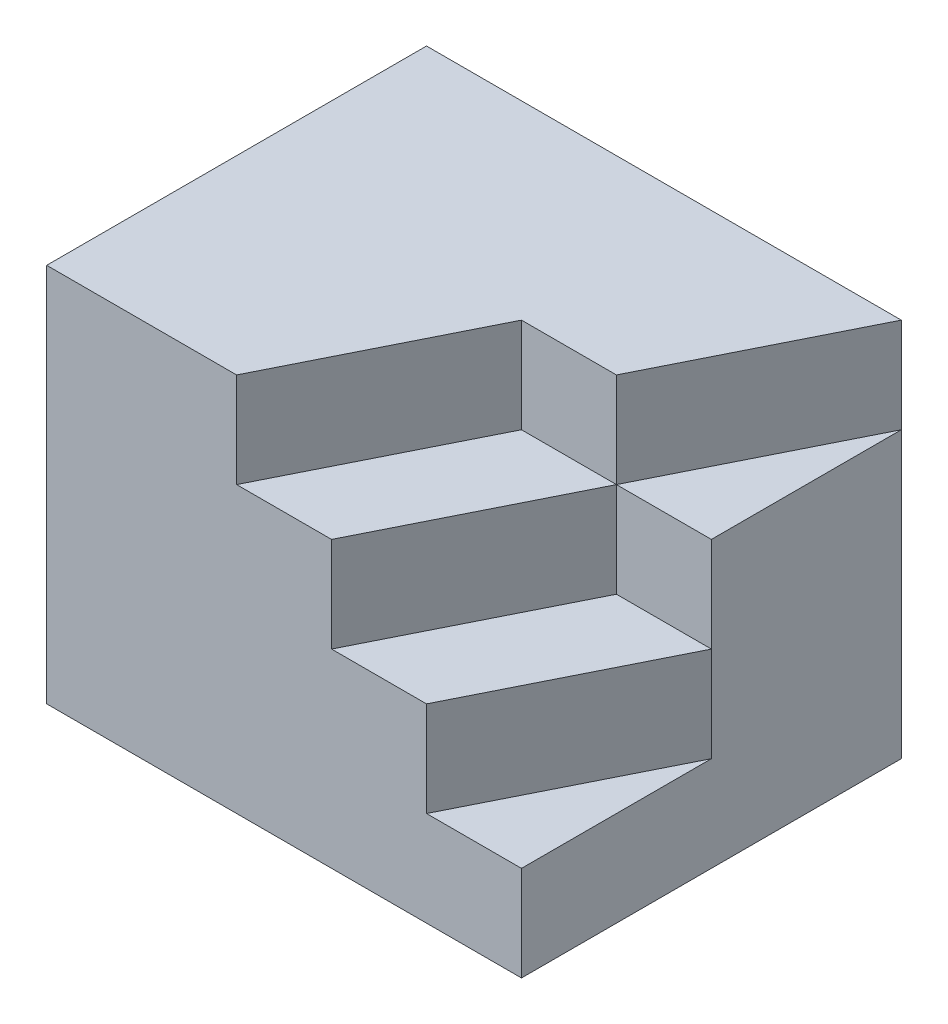
SolidWorks part; units mm, degrees
ref_plane "前基準面" through (0, 0, 0) normal (0, 0, 1) x (1, 0, 0)
ref_plane "上基準面" through (0, 0, 0) normal (0, 1, 0) x (1, 0, 0)
ref_plane "右基準面" through (0, 0, 0) normal (1, 0, 0) x (0, 0, -1)
sketch "草圖1" plane through (0, 0, 0) normal (0, 1, 0) x (1, 0, 0)
  line L1 (-25, -20) -> (25, -20)
  line L2 (-25, -20) -> (-25, 20)
  line L3 (-25, 20) -> (25, 20)
  line L4 (25, -20) -> (25, 20)
  line L5 (-25, -20) -> (25, 20) construction
  line L6 (-25, 20) -> (25, -20) construction
  point P0 (0, 0)
  dimension "D1" = 40
  dimension "D2" = 50
extrude "填料-伸長1" add sketch "草圖1" along normal blind 40
sketch "草圖2" plane through (0, 40, 0) normal (0, 1, 0) x (1, 0, 0)
  line L0 (25, 0) -> (15, -20)
  line L1 (25, -20) -> (25, 20) construction
  line L2 (-25, -20) -> (25, -20) construction
  line L3 (15, -20) -> (25, -20)
  line L4 (25, -20) -> (25, 0)
  dimension "D1" = 10
extrude "除料-伸長1" cut sketch "草圖2" against normal blind 30 contours L4 L0 L3
sketch "草圖3" plane through (0, 40, 0) normal (0, 1, 0) x (1, 0, 0)
  line L0 (25, 20) -> (5, -20)
  line L1 (-25, -20) -> (15, -20) construction
  line L2 (5, -20) -> (15, -20)
  line L3 (15, -20) -> (25, 0)
  line L4 (25, 0) -> (25, 20)
  line L5 (25, 0) -> (15, 0)
  line M2 (-25, -20) -> (15, -20)
  line M3 (15, -20) -> (25, 0)
  line M4 (25, 0) -> (25, 20)
  dimension "D1" = 10
extrude "除料-伸長2" cut sketch "草圖3" against normal blind 20 contours L5 L0 M3 M2 region at (15, 40, 10)
extrude "除料-伸長3" cut sketch "草圖3<3>" against normal blind 10 contours L5 L0 M4 region at (21.6667, 40, -6.6667)
sketch "草圖3<3>" plane through (0, 40, 0) normal (0, 1, 0) x (1, 0, 0) same geometry as "草圖3"
sketch "草圖4" plane through (0, 40, 0) normal (0, 1, 0) x (1, 0, 0)
  line L0 (15, 0) -> (5, 0)
  line L1 (5, 0) -> (-5, -20)
  line L2 (-25, -20) -> (5, -20) construction
  line L3 (-5, -20) -> (5, -20)
  dimension "D1" = 10
  dimension "D2" = 10
extrude "除料-伸長4" cut sketch "草圖4" against normal blind 10 and the other way through all
